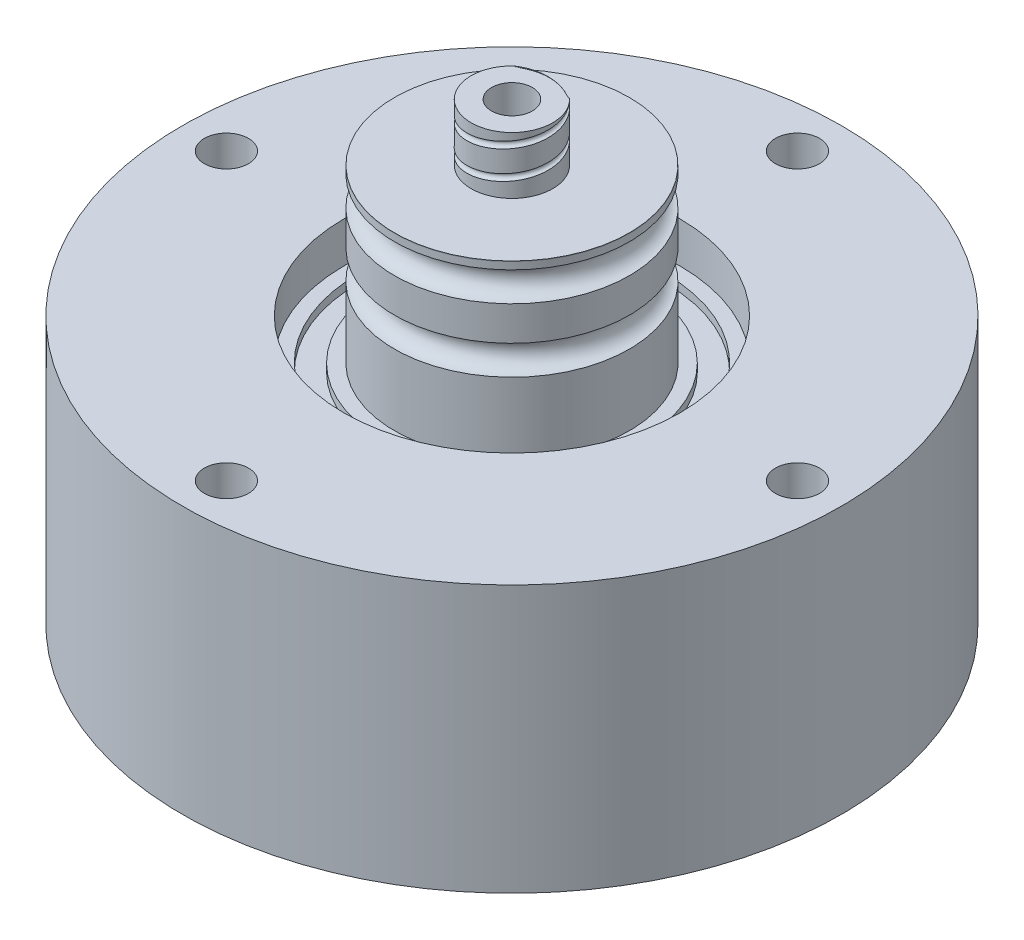
SolidWorks part; units mm, degrees
ref_plane "Front Plane" through (0, 0, 0) normal (0, 0, 1) x (1, 0, 0)
ref_plane "Top Plane" through (0, 0, 0) normal (0, 1, 0) x (1, 0, 0)
ref_plane "Right Plane" through (0, 0, 0) normal (1, 0, 0) x (0, 0, -1)
sketch "Sketch2" plane through (0, 0, 0) normal (1, 0, 0) x (0, 0, -1)
  line L0 (-51.308, 0) -> (51.308, 0) construction
  line L1 (0, 0) -> (0, 38.1) construction
  line L2 (8.9154, 33.02) -> (18.2782, 33.02)
  line L9 (18.288, 32.9502) -> (18.288, 31.8285)
  line L11 (18.288, 27.2565) -> (18.288, 21.9291)
  line L15 (26.162, 6.35) -> (26.162, 12.7)
  line L16 (26.162, 12.7) -> (51.308, 12.7)
  line L17 (51.308, 12.7) -> (51.308, 0)
  line L21 (18.288, 17.3571) -> (18.288, 6.35)
  line L30 (3.175, 25.365) -> (3.2167, -3.5015)
  line L39 (18.288, 31.8285) -> (0, 31.8285) construction
  line L43 (6.35, 33.02) -> (8.9154, 33.02)
  line L44 (3.175, 41.91) -> (6.35, 41.91)
  line L45 (51.308, 0) -> (51.308, -28.8664)
  line L46 (3.175, 38.065) -> (3.175, 25.365)
  line L47 (51.308, -28.8664) -> (37.338, -28.8664)
  line L48 (26.162, 6.35) -> (23.9649, 6.35)
  line L49 (23.9649, 6.35) -> (23.9649, 5.08)
  line L50 (23.9649, 5.08) -> (20.4089, 5.08)
  line L51 (20.4089, 5.08) -> (20.4089, 6.35)
  line L52 (20.4089, 6.35) -> (18.288, 6.35)
  line L53 (3.1912, -28.9015) -> (6.7472, -28.9015)
  line L54 (34.798, -26.3264) -> (34.798, -16.5087)
  line L55 (5.8493, -6.4359) -> (7.5062, -5.0024)
  line L56 (7.0012, -28.6475) -> (7.0012, -22.8055)
  line L57 (6.7472, -22.5515) -> (5.8238, -22.5515)
  line L58 (5.8238, -22.5515) -> (5.8238, -19.3765)
  line L59 (0, 0) -> (0, -28.8664) construction
  line L60 (5.8238, -19.3765) -> (6.8743, -16.5438)
  line L61 (6.6361, -16.2015) -> (5.8747, -16.2015)
  line L62 (5.8747, -16.2015) -> (5.8747, -12.9914)
  line L63 (5.8747, -12.9914) -> (6.9251, -10.1587)
  line L64 (6.687, -9.8164) -> (5.8493, -9.8164)
  line L65 (5.8493, -9.8164) -> (5.8493, -6.4359)
  line L66 (0.0417, -7.5645) -> (5.8493, -7.5645) construction
  line L67 (3.2167, -3.5015) -> (3.1912, -28.9015)
  line L71 (3.175, 41.91) -> (3.175, 38.065)
  line L72 (6.35, 41.91) -> (6.35, 33.02)
  arc A1 (18.288, 27.2565) -> (18.288, 31.8285) centre (18.288, 29.5425) cw
  arc A2 (18.288, 32.9502) -> (18.2782, 33.02) centre (18.034, 32.9502) ccw
  arc A4 (18.288, 21.9291) -> (18.288, 17.3571) centre (18.288, 19.6431) ccw
  arc A14 (6.6361, -16.2015) -> (6.8743, -16.5438) centre (6.6361, -16.4555) cw
  arc A15 (6.9251, -10.1587) -> (6.687, -9.8164) centre (6.687, -10.0704) ccw
  arc A16 (7.0012, -22.8055) -> (6.7472, -22.5515) centre (6.7472, -22.8055) ccw
  arc A17 (7.0012, -28.6475) -> (6.7472, -28.9015) centre (6.7472, -28.6475) cw
  arc A18 (7.5062, -5.0024) -> (34.798, -16.5087) centre (18.3119, -17.4921) cw
  arc A19 (37.338, -28.8664) -> (34.798, -26.3264) centre (37.338, -26.3264) cw
  point P3 (0, 0)
  point P96 (7.0267, -28.8664)
  dimension "D7" = 2.54
  dimension "D12" = 0.254
  dimension "D13" = 7.0012
  dimension "D31" = 0.254
  dimension "D32" = 0.254
  dimension "D33" = 0.254
  dimension "D4" = 12.7
  dimension "D5" = 6.35
  dimension "D6" = 7.874
  dimension "D8" = 3.175
  dimension "D9" = 3.175
  dimension "D10" = 37.338
  dimension "D11" = 51.308
  dimension "D21" = 18.288
  dimension "D28" = 3.556
  dimension "D29" = 3.175
  dimension "D30" = 1.27
  dimension "D34" = 5.8076
revolve "Revolve2" add sketch "Sketch2" angle 360 about L1
sketch "Sketch5" plane through (0, 41.91, 0) normal (0, 1, 0) x (1, 0, 0)
  circle A1 centre (0, 0) radius 6.35
curve "Helix/Spiral1" pitch 4.38 height 8.76 turns 2
sweep "Cut-Sweep1" cut path "Helix/Spiral1" align with end faces yes circular profile diameter 1.0414 parameters "D3"=1.0414
sketch "Sketch23" plane through (0, 0, 0) normal (0, 1, 0) x (1, 0, 0)
  circle A0 centre (0, 0) radius 44.45 construction
  circle A1 centre (0, 44.45) radius 3.429
extrude "Cut-Extrude1" cut sketch "Sketch23" against normal through all both and the other way through all
pattern_circular "CirPattern1" count 4 over 360 about axis through (0, 0, 0) along (0, 1, 0) of "Cut-Extrude1"
